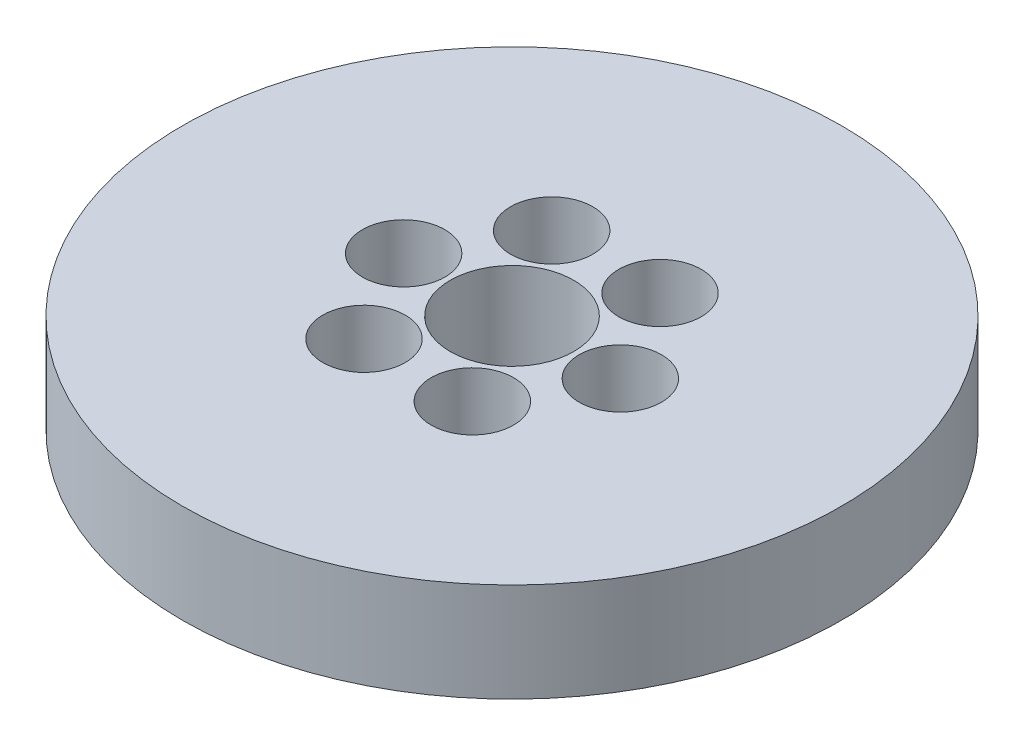
SolidWorks part; units mm, degrees
ref_plane "Front Plane" through (0, 0, 0) normal (0, 0, 1) x (1, 0, 0)
ref_plane "Top Plane" through (0, 0, 0) normal (0, 1, 0) x (1, 0, 0)
ref_plane "Right Plane" through (0, 0, 0) normal (1, 0, 0) x (0, 0, -1)
sketch "Sketch1" plane through (0, 0, 0) normal (0, 1, 0) x (1, 0, 0)
  circle A0 centre (0, 0) radius 80
  dimension "FLANGE_OD" = 160
extrude "Boss-Extrude1" add sketch "Sketch1" along normal blind 24
sketch "Sketch2" plane through (0, 0, 0) normal (0, 1, 0) x (1, 0, 0)
  circle A0 centre (0, 0) radius 15
  dimension "BORE_D" = 30
extrude "Cut-Extrude1" cut sketch "Sketch2" along normal through all
sketch "Sketch3" plane through (0, 24, 0) normal (0, 1, 0) x (1, 0, 0)
  circle A0 centre (0, 0) radius 26.3012 construction
  circle A1 centre (-26.3012, 0) radius 10
  dimension "BOLT_D" = 20
  dimension "BOLT_PCD" = 52.6023
extrude "Cut-Extrude2" cut sketch "Sketch3" against normal blind 14.5214
pattern_circular "CirPattern1" count 6 over 360 about axis through (0, 0, 0) along (0, 1, 0) of "Cut-Extrude2"
